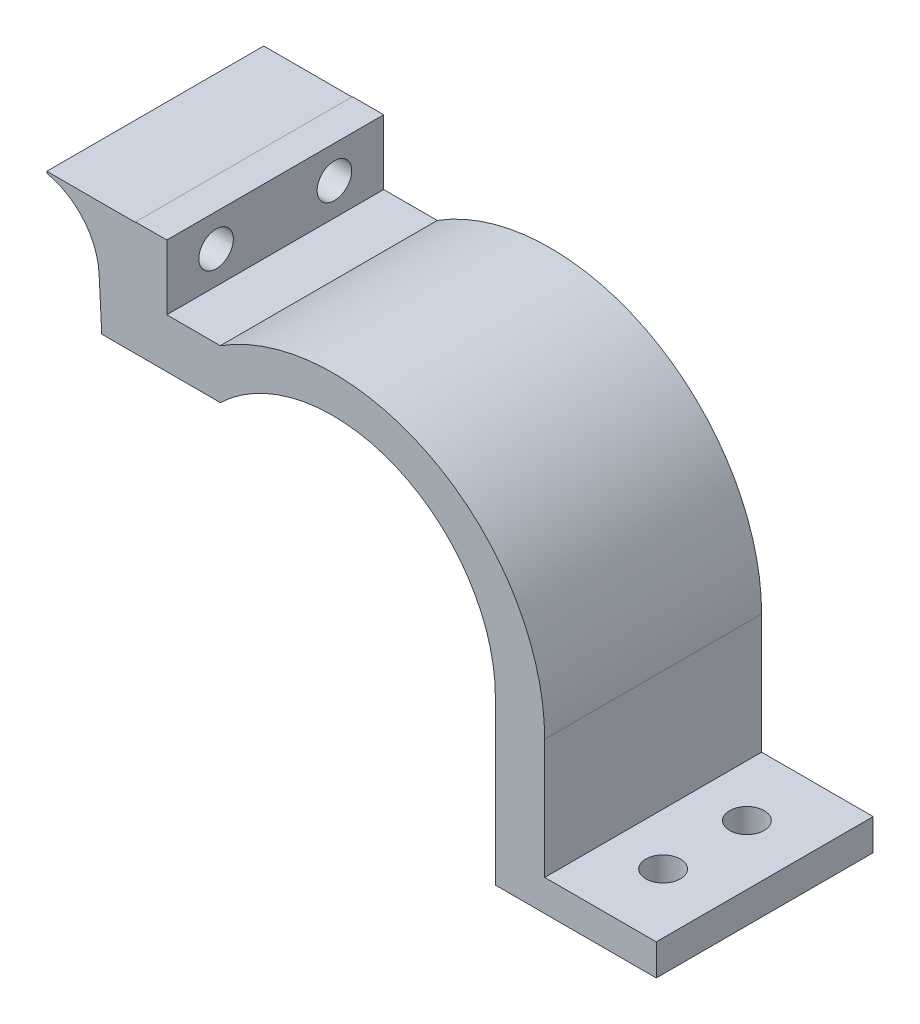
SolidWorks part; units mm, degrees
ref_plane "Front Plane" through (0, 0, 0) normal (0, 0, 1) x (1, 0, 0)
ref_plane "Top Plane" through (0, 0, 0) normal (0, 1, 0) x (1, 0, 0)
ref_plane "Right Plane" through (0, 0, 0) normal (1, 0, 0) x (0, 0, -1)
sketch "Sketch1" plane through (0, 0, 0) normal (0, 0, 1) x (1, 0, 0)
  line L0 (0, 0) -> (33.0033, 0) construction
  line L1 (33.0033, 0) -> (33.0033, -33)
  line L2 (33.0033, -33) -> (0, -33) construction
  line L3 (33.0033, -33) -> (65.6321, -33)
  line L4 (65.6321, -33) -> (65.6321, -26.65)
  line L5 (65.6321, -26.65) -> (43.0033, -26.65)
  line L6 (43.0033, -26.65) -> (43.0033, -2.3696)
  line L7 (0, 0) -> (-40, 0) construction
  line L8 (-40, 0) -> (-40, 50.6526) construction
  line L9 (-22.7938, 23.8598) -> (-40, 23.8598)
  line L10 (-40, 23.8598) -> (-40, 46.9951)
  line L11 (-40, 46.9951) -> (-33.65, 46.9951)
  line L12 (-33.65, 46.9951) -> (-33.65, 33.8598)
  line L13 (-33.65, 33.8598) -> (-22.7938, 33.8598)
  circle A0 centre (0, 0) radius 33 construction
  arc A1 (-22.7938, 23.8598) -> (33.0033, 0) centre (0.0033, 0) cw
  arc A2 (-22.7938, 33.8598) -> (43.0033, -2.3696) centre (0.1304, -2.3696) cw
  dimension "D1" = 10
  dimension "D4" = 33
  dimension "D2" = 6.35
  dimension "D3" = 6.35
  dimension "10" = 10
  dimension "D5" = 40
  dimension "D6" = 32.6288
  dimension "D7" = 23.1354
extrude "Boss-Extrude1" add sketch "Sketch1" against normal blind 44
sketch "Sketch2" plane through (0, -26.65, 0) normal (0, 1, 0) x (1, 0, 0)
  line L0 (53.5164, 34) -> (53.5164, 44) construction
  line L1 (65.6321, 44) -> (43.0033, 44) construction
  line L2 (53.5164, 10) -> (53.5164, 0) construction
  line L3 (65.6321, 0) -> (43.0033, 0) construction
  circle A0 centre (53.5164, 13.5) radius 3.5
  circle A2 centre (53.5164, 30.5) radius 3.5
extrude "Cut-Extrude1" cut sketch "Sketch2" against normal up to next
sketch "Sketch4" plane through (0, 0, 0) normal (0, 0, 1) x (1, 0, 0)
  line L0 (-40, 23.8598) -> (-46.8386, 23.8598)
  line L1 (-47.3809, 34.2065) -> (-44.4795, -21.1542) construction
  line L2 (-46.8386, 23.8598) -> (-47.3809, 34.2065)
  line L4 (-47.3764, 46.9048) -> (-40, 46.9048)
  line L5 (-40, 46.9951) -> (-40, 23.8598) construction
  line L6 (-40, 46.9048) -> (-40, 23.8598)
  line L7 (-47.3764, 46.9048) -> (-57.9858, 46.9048)
  line L8 (-57.9858, 46.9048) -> (-57.9858, 46.5446)
  arc A0 (-57.9858, 46.5446) -> (-47.3809, 34.2065) centre (-60.6709, 33.51) cw
extrude "Boss-Extrude2" add sketch "Sketch4" against normal up to surface (44 mm away) up to face at (9.0807, 10.4678, -44)
sketch "Sketch5" plane through (-33.65, 0, 0) normal (1, 0, 0) x (0, 0, -1)
  line L0 (0, 33.8598) -> (0, 46.9951) construction
  line L1 (44, 33.8598) -> (44, 46.9951) construction
  line L2 (44, 46.9951) -> (0, 46.9951) construction
  circle A0 centre (10, 40.4251) radius 3.5
  circle A1 centre (34, 40.4251) radius 3.5
  dimension "D1" = 7
  dimension "D2" = 7
  dimension "D3" = 10
  dimension "D4" = 10
  dimension "D5" = 6.57
extrude "Cut-Extrude2" cut sketch "Sketch5" against normal up to next
